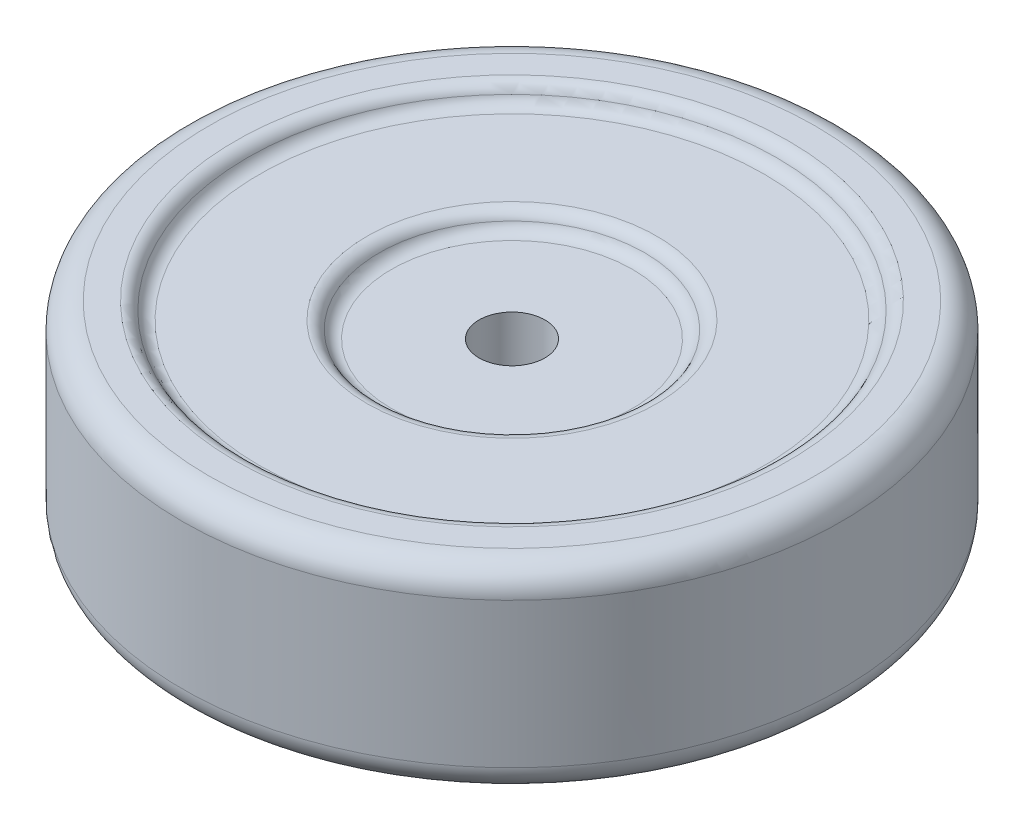
SolidWorks part; units mm, degrees
ref_plane "Front Plane" through (0, 0, 0) normal (0, 0, 1) x (1, 0, 0)
ref_plane "Top Plane" through (0, 0, 0) normal (0, 1, 0) x (1, 0, 0)
ref_plane "Right Plane" through (0, 0, 0) normal (1, 0, 0) x (0, 0, -1)
sketch "Sketch1" plane through (0, 0, 0) normal (0, 1, 0) x (1, 0, 0)
  circle A0 centre (0, 0) radius 127
extrude "Boss-Extrude1" add sketch "Sketch1" along normal blind 38.1
sketch "Sketch2" plane through (0, 38.1, 0) normal (0, 1, 0) x (1, 0, 0)
  circle A0 centre (0, 0) radius 101.6
extrude "Cut-Extrude1" cut sketch "Sketch2" against normal blind 6.35
sketch "Sketch3" plane through (0, 31.75, 0) normal (0, 1, 0) x (1, 0, 0)
  circle A0 centre (0, 0) radius 50.8
extrude "Cut-Extrude2" cut sketch "Sketch3" against normal blind 6.35
sketch "Sketch4" plane through (0, 25.4, 0) normal (0, 1, 0) x (1, 0, 0)
  circle A0 centre (0, 0) radius 12.7
  dimension "D1" = 25.4
extrude "Cut-Extrude3" cut sketch "Sketch4" against normal blind 77.978
fillet "Fillet1" radius 10.16 1 edges at (0, 38.1, 127)
fillet "Fillet2" radius 5.08 1 edges at (0, 38.1, 101.6)
fillet "Fillet3" radius 5.08 1 edges at (0, 31.75, 101.6)
fillet "Fillet4" radius 5.08 1 edges at (0, 31.75, 50.8)
fillet "Fillet5" radius 5.08 1 edges at (0, 25.4, 50.8)
mirror "Mirror1" about plane through (0, 0, 0) normal (0, 1, 0) of "Fillet5", "Fillet4", "Fillet3", "Fillet2", "Fillet1", "Cut-Extrude2", "Cut-Extrude3", "Cut-Extrude1", "Boss-Extrude1"
